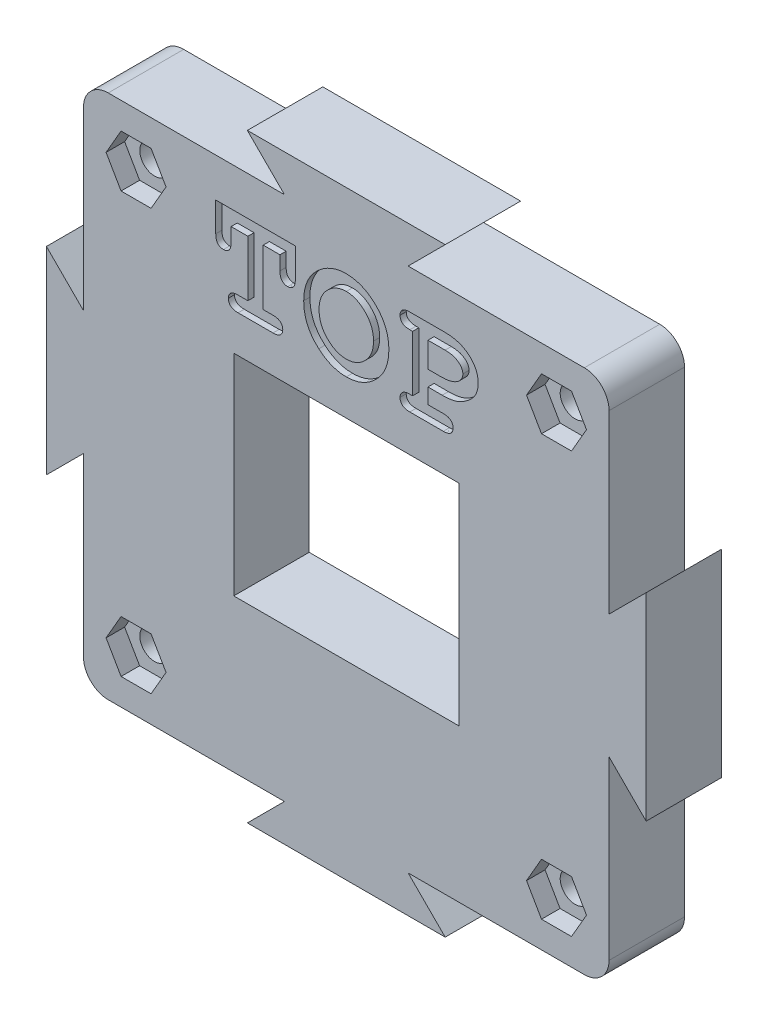
SolidWorks part; units mm, degrees
ref_plane "Front Plane" through (0, 0, 0) normal (0, 0, 1) x (1, 0, 0)
ref_plane "Top Plane" through (0, 0, 0) normal (0, 1, 0) x (1, 0, 0)
ref_plane "Right Plane" through (0, 0, 0) normal (1, 0, 0) x (0, 0, -1)
sketch "Sketch1" plane through (0, 0, 0) normal (0, 0, 1) x (1, 0, 0)
  line L4 (-5, 21.25) -> (-19.25, 21.25)
  line L5 (-5, 21.25) -> (-19.25, 21.25)
  line L6 (-21.25, 19.25) -> (-21.25, 5)
  line L7 (-21.25, 19.25) -> (-21.25, 5)
  line L21 (-8.9, -8.7) -> (8.9, -8.7) construction
  line L22 (-8.9, 7.9) -> (-8.9, -8.7) construction
  line L23 (8.9, 7.9) -> (-8.9, 7.9) construction
  line L24 (8.9, -8.7) -> (8.9, 7.9) construction
  line L25 (-8.9, -8.7) -> (8.9, -8.7) construction
  line L26 (-8.9, 7.9) -> (-8.9, -8.7) construction
  line L27 (8.9, 7.9) -> (-8.9, 7.9) construction
  line L28 (8.9, -8.7) -> (8.9, 7.9) construction
  line L29 (-9.1, -8.9) -> (9.1, -8.9)
  line L30 (9.1, -8.9) -> (9.1, 8.1)
  line L31 (9.1, 8.1) -> (-9.1, 8.1)
  line L32 (-9.1, 8.1) -> (-9.1, -8.9)
  line L50 (-21.25, 5) -> (-24.25, 8)
  line L51 (-21.25, 5) -> (-24.25, 8)
  line L52 (-24.25, 8) -> (-24.25, -8)
  line L53 (-24.25, 8) -> (-24.25, -8)
  line L54 (-24.25, -8) -> (-21.25, -5)
  line L55 (-24.25, -8) -> (-21.25, -5)
  line L56 (-21.25, -5) -> (-21.25, -19.25)
  line L57 (-21.25, -5) -> (-21.25, -19.25)
  line L58 (-19.25, -21.25) -> (-5, -21.25)
  line L59 (-19.25, -21.25) -> (-5, -21.25)
  line L60 (-5, -21.25) -> (-8, -24.25)
  line L61 (-5, -21.25) -> (-8, -24.25)
  line L62 (-8, -24.25) -> (8, -24.25)
  line L63 (-8, -24.25) -> (8, -24.25)
  line L64 (8, -24.25) -> (5, -21.25)
  line L65 (8, -24.25) -> (5, -21.25)
  line L66 (5, -21.25) -> (19.25, -21.25)
  line L67 (5, -21.25) -> (19.25, -21.25)
  line L68 (21.25, -19.25) -> (21.25, -5)
  line L69 (21.25, -19.25) -> (21.25, -5)
  line L70 (21.25, -5) -> (24.25, -8)
  line L71 (21.25, -5) -> (24.25, -8)
  line L72 (24.25, -8) -> (24.25, 8)
  line L73 (24.25, -8) -> (24.25, 8)
  line L74 (24.25, 8) -> (21.25, 5)
  line L75 (24.25, 8) -> (21.25, 5)
  line L76 (21.25, 5) -> (21.25, 19.25)
  line L77 (21.25, 5) -> (21.25, 19.25)
  line L78 (19.25, 21.25) -> (5, 21.25)
  line L79 (19.25, 21.25) -> (5, 21.25)
  line L80 (5, 21.25) -> (8, 24.25)
  line L81 (5, 21.25) -> (8, 24.25)
  line L82 (8, 24.25) -> (-8, 24.25)
  line L83 (8, 24.25) -> (-8, 24.25)
  line L84 (-8, 24.25) -> (-5, 21.25)
  line L85 (-8, 24.25) -> (-5, 21.25)
  circle A0 centre (-17, -17) radius 1.2 construction
  circle A1 centre (17, -17) radius 1.2 construction
  circle A2 centre (17, 17) radius 1.2 construction
  circle A3 centre (-17, 17) radius 1.2 construction
  arc A4 (-19.25, 21.25) -> (-21.25, 19.25) centre (-19.25, 19.25) ccw
  arc A5 (-19.25, 21.25) -> (-21.25, 19.25) centre (-19.25, 19.25) ccw
  arc A6 (-21.25, -19.25) -> (-19.25, -21.25) centre (-19.25, -19.25) ccw
  arc A7 (-21.25, -19.25) -> (-19.25, -21.25) centre (-19.25, -19.25) ccw
  circle A12 centre (-17, -17) radius 1.2
  circle A13 centre (17, -17) radius 1.2
  circle A14 centre (17, 17) radius 1.2
  circle A15 centre (-17, 17) radius 1.2
  arc A20 (19.25, -21.25) -> (21.25, -19.25) centre (19.25, -19.25) ccw
  arc A21 (19.25, -21.25) -> (21.25, -19.25) centre (19.25, -19.25) ccw
  arc A22 (21.25, 19.25) -> (19.25, 21.25) centre (19.25, 19.25) ccw
  arc A23 (21.25, 19.25) -> (19.25, 21.25) centre (19.25, 19.25) ccw
  dimension "D2" = 16
  dimension "D3" = 0.2
  dimension "D1" = 0
extrude "Boss-Extrude1" add sketch "Sketch1" along normal blind 6.1
sketch "Sketch2" plane through (0, 0, 0) normal (0, 0, -1) x (-1, 0, 0)
  line L0 (-9.5, 17) -> (9.5, 17) construction
  line L1 (-9.5, 18.25) -> (9.5, 18.25)
  line L2 (-9.5, 15.75) -> (9.5, 15.75)
  line L3 (-9.5, 16) -> (-9.5, 18) construction
  line L4 (9.5, 18) -> (9.5, 16) construction
  arc A0 (-9.5, 18.25) -> (-9.5, 15.75) centre (-9.5, 17) ccw
  arc A1 (9.5, 15.75) -> (9.5, 18.25) centre (9.5, 17) ccw
  point P2 (0, 17)
  point P7 (-17, 17)
  dimension "D1" = 2.5
extrude "Cut-Extrude3" cut sketch "Sketch2" against normal blind 1
sketch "Sketch3" plane through (0, 0, 6.1) normal (0, 0, 1) x (1, 0, 0)
  line L0 (-18.2124, -14.9) -> (-19.4249, -17)
  line L1 (15.7876, -14.9) -> (14.5751, -17)
  line L2 (14.5751, -17) -> (15.7876, -19.1)
  line L3 (15.7876, -19.1) -> (18.2124, -19.1)
  line L4 (18.2124, -19.1) -> (19.4249, -17)
  line L5 (19.4249, -17) -> (18.2124, -14.9)
  line L6 (18.2124, -14.9) -> (15.7876, -14.9)
  line L7 (-19.4249, -17) -> (-18.2124, -19.1)
  line L8 (-18.2124, -19.1) -> (-15.7876, -19.1)
  line L9 (-15.7876, -19.1) -> (-14.5751, -17)
  line L10 (-14.5751, -17) -> (-15.7876, -14.9)
  line L11 (-15.7876, -14.9) -> (-18.2124, -14.9)
  line L12 (-18.2124, 19.1) -> (-19.4249, 17)
  line L13 (-19.4249, 17) -> (-18.2124, 14.9)
  line L14 (-18.2124, 14.9) -> (-15.7876, 14.9)
  line L15 (-15.7876, 14.9) -> (-14.5751, 17)
  line L16 (-14.5751, 17) -> (-15.7876, 19.1)
  line L17 (-15.7876, 19.1) -> (-18.2124, 19.1)
  line L18 (15.7876, 19.1) -> (14.5751, 17)
  line L19 (14.5751, 17) -> (15.7876, 14.9)
  line L20 (15.7876, 14.9) -> (18.2124, 14.9)
  line L21 (18.2124, 14.9) -> (19.4249, 17)
  line L22 (19.4249, 17) -> (18.2124, 19.1)
  line L23 (18.2124, 19.1) -> (15.7876, 19.1)
  line L24 (15.7876, -14.9) -> (-18.2124, -14.9) construction
  line L25 (15.7876, -14.9) -> (15.7876, 19.1) construction
  circle A0 centre (17, -17) radius 2.1 construction
  circle A1 centre (-17, -17) radius 2.1 construction
  circle A2 centre (-17, 17) radius 2.1 construction
  circle A3 centre (17, 17) radius 2.1 construction
  dimension "D1" = 4.2
  dimension "D2" = 2
  dimension "D4" = 90
  dimension "D3" = 2
extrude "Cut-Extrude4" cut sketch "Sketch3" against normal blind 1.5
sketch "Sketch4" plane through (0, 0, 6.1) normal (0, 0, 1) x (1, 0, 0)
  line L0 (-21.25, 11.1) -> (21.25, 11.1) construction
  line L4 (-21.25, 19.25) -> (-21.25, 5) construction
  line L5 (21.25, 5) -> (21.25, 19.25) construction
  line L6 (9.1, 8.1) -> (-9.1, 8.1) construction
  text T0 "<b>TOP</b>" font "Courier New" height 7
  point P3 (-21.25, 11.1)
  point P6 (21.25, 11.1)
  dimension "D1" = 3
extrude "Cut-Extrude5" cut sketch "Sketch4" against normal blind 0.5
